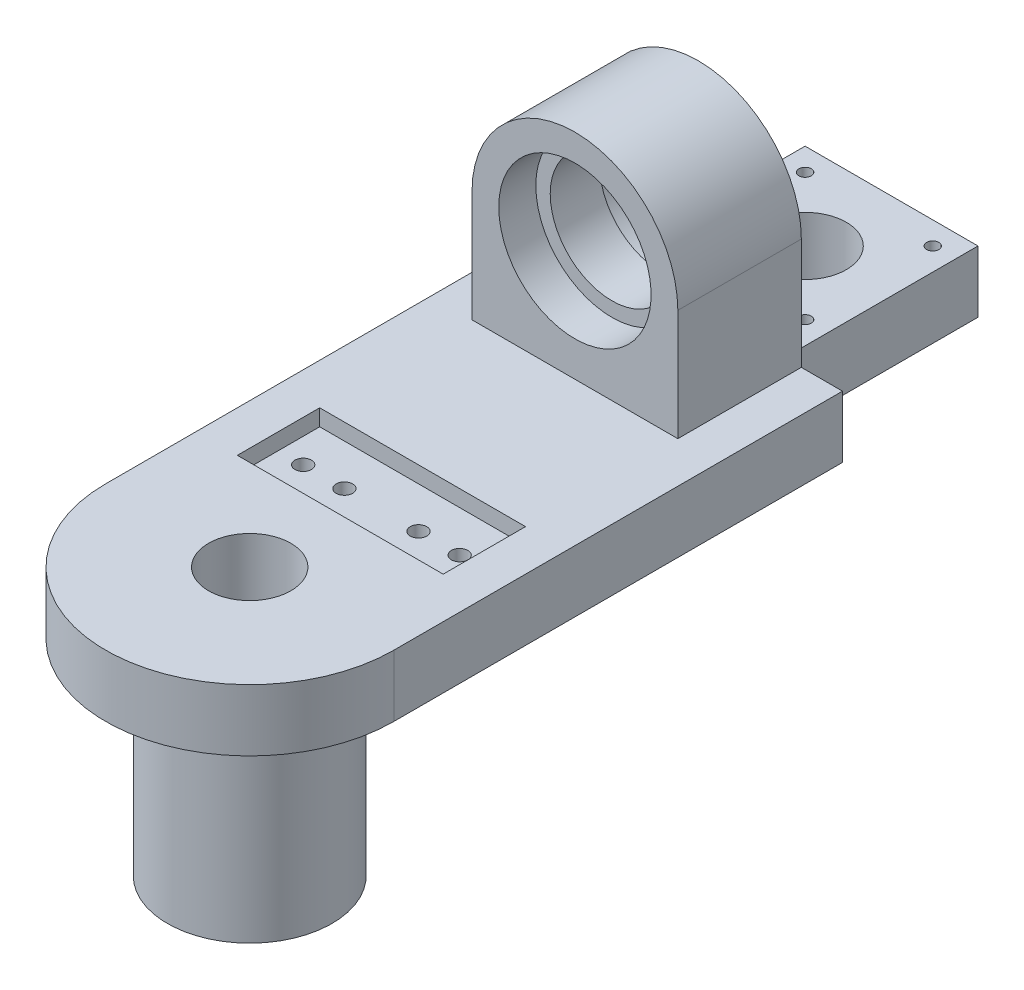
SolidWorks part; units mm, degrees
ref_plane "Ebene vorne" through (0, 0, 0) normal (0, 0, 1) x (1, 0, 0)
ref_plane "Ebene oben" through (0, 0, 0) normal (0, 1, 0) x (1, 0, 0)
ref_plane "Ebene rechts" through (0, 0, 0) normal (1, 0, 0) x (0, 0, -1)
sketch "Skizze1" plane through (0, 0, 0) normal (0, 1, 0) x (1, 0, 0)
  line L0 (-25.9794, -35) -> (25.9794, -35) construction
  line L1 (-35, 0) -> (35, 0)
  line L2 (-35, 0) -> (-35, 109)
  line L4 (35, 0) -> (35, 109)
  line L5 (-35, 0) -> (35, 109) construction
  line L6 (-35, 109) -> (35, 0) construction
  line L9 (-35, 109) -> (-35, 78)
  line L12 (-35, 109) -> (35, 109)
  line L13 (-21.0848, 156) -> (20.9152, 114) construction
  line L21 (-21.0848, 109) -> (20.9152, 109)
  line L22 (-21.0848, 109) -> (-21.0848, 156)
  line L23 (-21.0848, 156) -> (20.9152, 156)
  line L24 (20.9152, 109) -> (20.9152, 156)
  line L25 (20.9152, 156) -> (-21.0848, 114) construction
  circle A0 centre (0, 0) radius 35
  circle A2 centre (-0.0848, 135) radius 10
  circle A3 centre (-15.5848, 150.5) radius 1.5
  circle A4 centre (15.4152, 150.5) radius 1.5
  circle A5 centre (15.4152, 119.5) radius 1.5
  circle A6 centre (-15.5848, 119.5) radius 1.5
  point P7 (0, 54.5)
  point P11 (0, -35)
  point P31 (-0.0848, 135)
  dimension "D1" = 70
  dimension "D5" = 144
  dimension "D4" = 42
  dimension "D6" = 4
  dimension "D2" = 42
  dimension "D3" = 5
extrude "Aufsatz-Linear austragen1" add sketch "Skizze1" along normal blind 15
sketch "Skizze2" plane through (0, 15, 0) normal (0, 1, 0) x (1, 0, 0)
  line L0 (-35, 109) -> (-21.0848, 109) construction
  line L1 (25, 109) -> (-25, 109)
  line L2 (25, 109) -> (25, 79)
  line L3 (25, 79) -> (-25, 79)
  line L4 (-25, 109) -> (-25, 79)
  line L5 (25, 109) -> (-25, 79) construction
  line L6 (25, 79) -> (-25, 109) construction
  point P4 (0, 94)
  dimension "D1" = 50
  dimension "D2" = 30
extrude "Aufsatz-Linear austragen2" add sketch "Skizze2" along normal blind 52
sketch "Skizze3" plane through (0, 0, -109) normal (0, 0, -1) x (-1, 0, 0)
  line L0 (-25, 67) -> (25, 67) construction
  line L5 (-25, 67) -> (25, 67)
  line L8 (25, 67) -> (25, 17)
  line L9 (-25, 67) -> (25, 17) construction
  line L10 (-25, 17) -> (25, 67) construction
  line L12 (-25, 42) -> (-25, 67)
  line L13 (25, 67) -> (-25, 67)
  line L14 (-25, 67) -> (-25, 15) construction
  line L15 (25, 67) -> (25, 42)
  line L16 (-25, 67) -> (-25, 17)
  line L17 (25, 67) -> (25, 15) construction
  line L18 (35, 15) -> (25, 15) construction
  circle A1 centre (0, 42) radius 15
  circle A2 centre (0, 42) radius 25
  point P4 (0, 42)
  line M10 (25, 67) -> (-25, 67)
  line M15 (-25, 67) -> (-25, 15)
  dimension "D1" = 2
extrude "Schnitt-Linear austragen9" cut sketch "Skizze3" against normal blind 30 contours A1 | A2 L13 M15 | A2 L8 M10 region at (19.4158, 61.4158, -109) region at (-19.4158, 61.4158, -109) region at (0, 42, -109)
sketch "Skizze4" plane through (0, 0, -109) normal (0, 0, -1) x (-1, 0, 0)
  line L9 (25, 42) -> (25, 15) construction
  line L10 (-25, 17) -> (25, 17)
  line L11 (-25, 17) -> (-25, 67)
  line L12 (25, 42) -> (25, 15) construction
  line L14 (-25, 17) -> (25, 17)
  line L17 (35, 15) -> (25, 15) construction
  line L18 (-25, 67) -> (25, 67)
  line L19 (25, 17) -> (25, 67)
  line L20 (-25, 42) -> (-25, 15) construction
  line L21 (-25, 67) -> (25, 17) construction
  line L22 (25, 67) -> (-25, 17) construction
  arc A3 (25, 42) -> (-25, 42) centre (0, 42) ccw construction
  circle A4 centre (0, 42) radius 18.5
  dimension "D1" = 37
  dimension "D2" = 2
  dimension "D3" = 50
extrude "Schnitt-Linear austragen10" cut sketch "Skizze4" against normal blind 9 contours A4
ref_plane "Ebene1" through (0, 0, -94) normal (0, 0, -1) x (-1, 0, 0)
sketch "Skizze5" plane through (0, 15, 0) normal (0, 1, 0) x (1, 0, 0)
  line L0 (35, 0) -> (35, 109) construction
  line L1 (-25, 79) -> (35, 79)
  line L2 (-25, 79) -> (-25, 42)
  line L3 (-25, 42) -> (35, 42)
  line L4 (35, 79) -> (35, 42)
  line L5 (-25, 79) -> (35, 42) construction
  line L6 (-25, 42) -> (35, 79) construction
  line L7 (0, 0) -> (0, 32) construction
  line L8 (-25, 42) -> (35, 42)
  line L14 (-25, 22) -> (25, 22)
  line L15 (-25, 22) -> (-25, 42)
  line L16 (-25, 42) -> (25, 42)
  line L17 (25, 22) -> (25, 42)
  line L18 (-25, 22) -> (25, 42) construction
  line L19 (-25, 42) -> (25, 22) construction
  point P4 (5, 60.5)
  point P13 (0, 32)
  dimension "D1" = 20
  dimension "D2" = 37
  dimension "D3" = 50
extrude "Schnitt-Linear austragen3" cut sketch "Skizze5" against normal blind 4 contours L14 L17 L3 L16 L15 region at (0, 15, -32)
sketch "Skizze6" plane through (0, 11, 0) normal (0, 1, 0) x (1, 0, 0)
  line L0 (-25, 32) -> (25, 32) construction
  line L3 (0, 32) -> (0, 3.2798) construction
  line L5 (25, 22) -> (25, 42) construction
  circle A0 centre (9, 32) radius 2
  circle A1 centre (-9, 32) radius 2
  circle A2 centre (19, 32) radius 2
  circle A3 centre (-19, 32) radius 2
  dimension "D2" = 4
  dimension "D3" = 4
  dimension "D4" = 10
extrude "Schnitt-Linear austragen4" cut sketch "Skizze6" against normal blind 11
sketch "Skizze8" plane through (0, 0, 0) normal (0, -1, 0) x (1, 0, 0)
  circle A0 centre (0, 0) radius 20
  circle A1 centre (0, 0) radius 32.5
  circle A2 centre (0, 0) radius 26.25
  dimension "D1" = 40
  dimension "D2" = 65
  dimension "D3" = 52.5
extrude "Schnitt-Linear austragen5" cut sketch "Skizze8" against normal blind 4 contours A1 A2 region at (-31.5808, 0, 0)
sketch "Skizze10" plane through (0, 0, 0) normal (0, -1, 0) x (1, 0, 0)
  circle A0 centre (0, 0) radius 20
extrude "Aufsatz-Linear austragen3" add sketch "Skizze10" along normal blind 50 contours A0
sketch "Skizze11" plane through (0, 0, 0) normal (0, -1, 0) x (1, 0, 0)
  circle A0 centre (9, -32) radius 3.5
  circle A1 centre (19, -32) radius 3.5
  circle A2 centre (-19, -32) radius 3.5
  circle A3 centre (-9, -32) radius 3.5
  dimension "D1" = 7
  dimension "D2" = 7
extrude "Schnitt-Linear austragen6" cut sketch "Skizze11" against normal offset from surface (8 mm away) 8 up to face at (-19, 0, -34)
sketch "Skizze12" plane through (0, -50, 0) normal (0, -1, 0) x (1, 0, 0)
  circle A0 centre (0, 0) radius 10
  circle A1 centre (0, 0) radius 20 construction
  dimension "D1" = 10
extrude "Schnitt-Linear austragen7" cut sketch "Skizze12" against normal blind 65
sketch "Skizze13" plane through (0, -50, 0) normal (0, -1, 0) x (1, 0, 0)
  line L0 (10, 0) -> (20, 0) construction
  circle A0 centre (0, 0) radius 10 construction
  circle A1 centre (0, 0) radius 20 construction
  circle A3 centre (15, 0) radius 2
  circle A4 centre (7.5, -12.9904) radius 2
  circle A5 centre (-7.5, -12.9904) radius 2
  circle A6 centre (-15, 0) radius 2
  circle A7 centre (-7.5, 12.9904) radius 2
  circle A8 centre (7.5, 12.9904) radius 2
  point P21 (0, 0)
  dimension "D1" = 6
extrude "Schnitt-Linear austragen8" cut sketch "Skizze13" against normal blind 15
mirror "Spiegeln2" about plane through (0, 0, -94) normal (0, 0, -1) of "Schnitt-Linear austragen10"
ref_plane "Plane1" through (25, 15, -79) normal (1, 0, 0) x (0, 0, -1)
